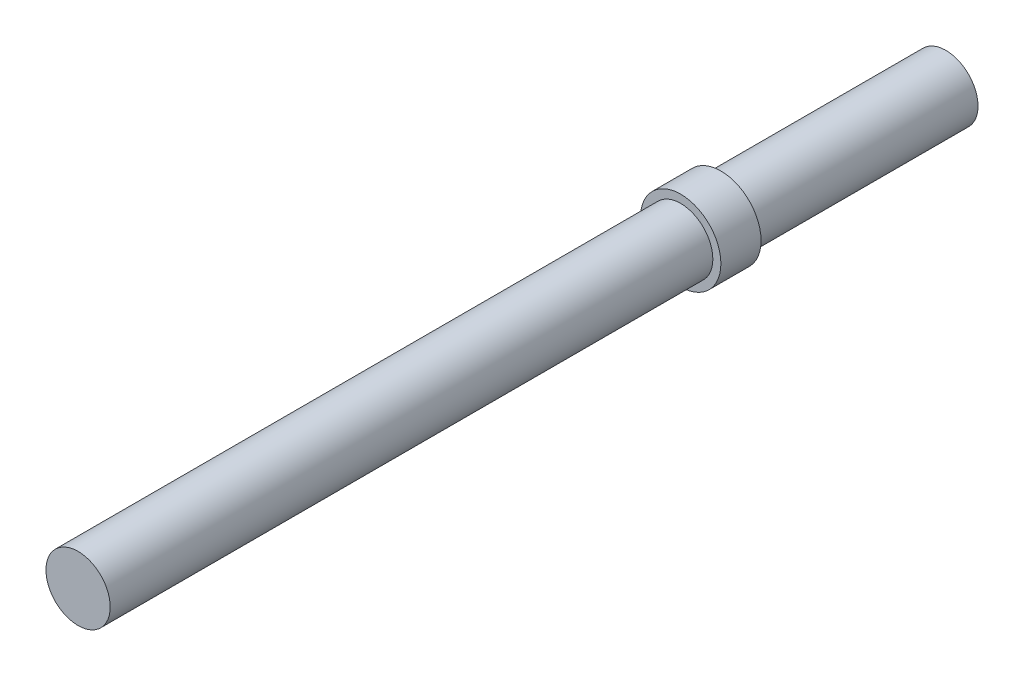
SolidWorks part; units mm, degrees
ref_plane "Alzado" through (0, 0, 0) normal (0, 0, 1) x (1, 0, 0)
ref_plane "Planta" through (0, 0, 0) normal (0, 1, 0) x (1, 0, 0)
ref_plane "Vista lateral" through (0, 0, 0) normal (1, 0, 0) x (0, 0, -1)
sketch "Croquis1" plane through (0, 0, 0) normal (0, 0, 1) x (1, 0, 0)
  circle A0 centre (0, 0) radius 4
  dimension "D1" = 8
extrude "Saliente-Extruir1" add sketch "Croquis1" along normal mid plane 108
ref_plane "Plano2" through (3, 0, 0) normal (1, 0, 0) x (0, 0, -1)
ref_plane "Plano3" through (0, 0, -26) normal (0, 0, 1) x (1, 0, 0)
sketch "Croquis2" plane through (0, 0, -26) normal (0, 0, 1) x (1, 0, 0)
  circle A0 centre (0, 0) radius 5
  dimension "D1" = 10
extrude "Saliente-Extruir2" add sketch "Croquis2" along normal blind 5
